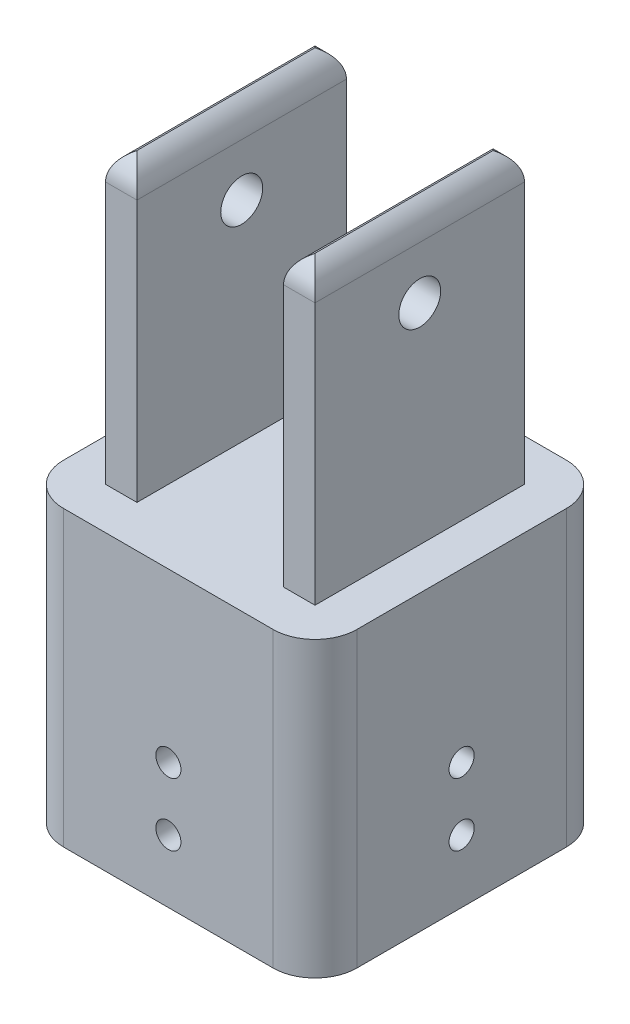
SolidWorks part; units mm, degrees
ref_plane "Front Plane" through (0, 0, 0) normal (0, 0, 1) x (1, 0, 0)
ref_plane "Top Plane" through (0, 0, 0) normal (0, 1, 0) x (1, 0, 0)
ref_plane "Right Plane" through (0, 0, 0) normal (1, 0, 0) x (0, 0, -1)
sketch "Sketch1" plane through (0, 0, 0) normal (0, 1, 0) x (1, 0, 0)
  line L0 (0, 0) -> (50, 0)
  line L1 (50, 0) -> (50, 50)
  line L2 (50, 50) -> (0, 50)
  line L3 (0, 50) -> (0, 0)
extrude "Boss-Extrude1" add sketch "Sketch1" along normal blind 70
sketch "Sketch3" plane through (0, 70, 0) normal (0, 1, 0) x (1, 0, 0)
  line L1 (50, 50) -> (0, 50) construction
  line L2 (7.5, 50) -> (42.5, 50)
  line L3 (42.5, 50) -> (42.5, 0)
  line L4 (0, 0) -> (50, 0) construction
  line L5 (42.5, 0) -> (7.5, 0)
  line L6 (7.5, 0) -> (7.5, 50)
extrude "Cut-Extrude1" cut sketch "Sketch3" against normal blind 120
sketch "Sketch4" plane through (0, 0, 0) normal (-1, 0, 0) x (0, 0, 1)
  circle A0 centre (-25, 50) radius 5
extrude "Cut-Extrude2" cut sketch "Sketch4" against normal blind 14
fillet "Fillet2" radius 7.5 4 edges at (46.25, 70, -50) (50, 70, -25) (46.25, 70, 0) (42.5, 70, -25)
sketch "Sketch6" plane through (0, 0, 0) normal (0, -1, 0) x (-1, 0, 0)
  line L1 (-60, 0) -> (-60, -10)
  line L2 (-60, -10) -> (10, -10)
  line L3 (10, -10) -> (10, 60)
  line L4 (10, 60) -> (-60, 60)
  line L5 (-60, 60) -> (-60, 0)
extrude "Boss-Extrude2" add sketch "Sketch6" along normal blind 70
fillet "Fillet4" radius 10 4 edges at (60, -35, 10) (-10, -35, -60) (-10, -35, 10) (60, -35, -60)
sketch "Sketch15" plane through (0, -70, 0) normal (0, -1, 0) x (1, 0, 0)
  line L0 (10, 0) -> (40, 0)
  line L1 (50, -10) -> (50, -40)
  line L2 (40, -50) -> (10, -50)
  line L3 (0, -40) -> (0, -10)
  arc A0 (10, -50) -> (0, -40) centre (10, -40) cw
  arc A1 (40, -50) -> (50, -40) centre (40, -40) ccw
  arc A2 (50, -10) -> (40, 0) centre (40, -10) ccw
  arc A3 (10, 0) -> (0, -10) centre (10, -10) ccw
  point P13 (0, 0)
  dimension "D1" = 10
extrude "Cut-Extrude10" cut sketch "Sketch15" against normal blind 45
sketch "Sketch10" plane through (-10, 0, 0) normal (-1, 0, 0) x (0, 0, 1)
  circle A0 centre (-25, -40) radius 3
  circle A1 centre (-25, -55) radius 3
extrude "Cut-Extrude6" cut sketch "Sketch10" against normal blind 10
sketch "Sketch12" plane through (0, 0, -60) normal (0, 0, -1) x (-1, 0, 0)
  circle A2 centre (-25, -40) radius 3
  circle A3 centre (-25, -55) radius 3
extrude "Cut-Extrude7" cut sketch "Sketch12" against normal blind 10
sketch "Sketch13" plane through (60, 0, 0) normal (1, 0, 0) x (0, 0, -1)
  circle A2 centre (25, -40) radius 3
  circle A3 centre (25, -55) radius 3
  point P1 (24.7468, -55)
  point P7 (0, 0)
  point P8 (0, 0)
  point P9 (24.6074, -40)
extrude "Cut-Extrude8" cut sketch "Sketch13" against normal blind 10
sketch "Sketch14" plane through (0, 0, 10) normal (0, 0, 1) x (1, 0, 0)
  circle A0 centre (25, -40) radius 3
  circle A1 centre (25, -55) radius 3
extrude "Cut-Extrude9" cut sketch "Sketch14" against normal blind 10
fillet "Fillet5" radius 7.5 4 edges at (3.75, 70, -50) (3.75, 70, 0) (0, 70, -25) (7.5, 70, -25)
sketch "Sketch16" plane through (42.5, 0, 0) normal (-1, 0, 0) x (0, 0, 1)
  circle A0 centre (-25, 50) radius 5
extrude "Cut-Extrude12" cut sketch "Sketch16" against normal blind 10
sketch "Sketch17" plane through (0, 0, 0) normal (0, 1, 0) x (1, 0, 0)
  circle A0 centre (25, 25) radius 5
extrude "Cut-Extrude13" cut sketch "Sketch17" against normal blind 50
